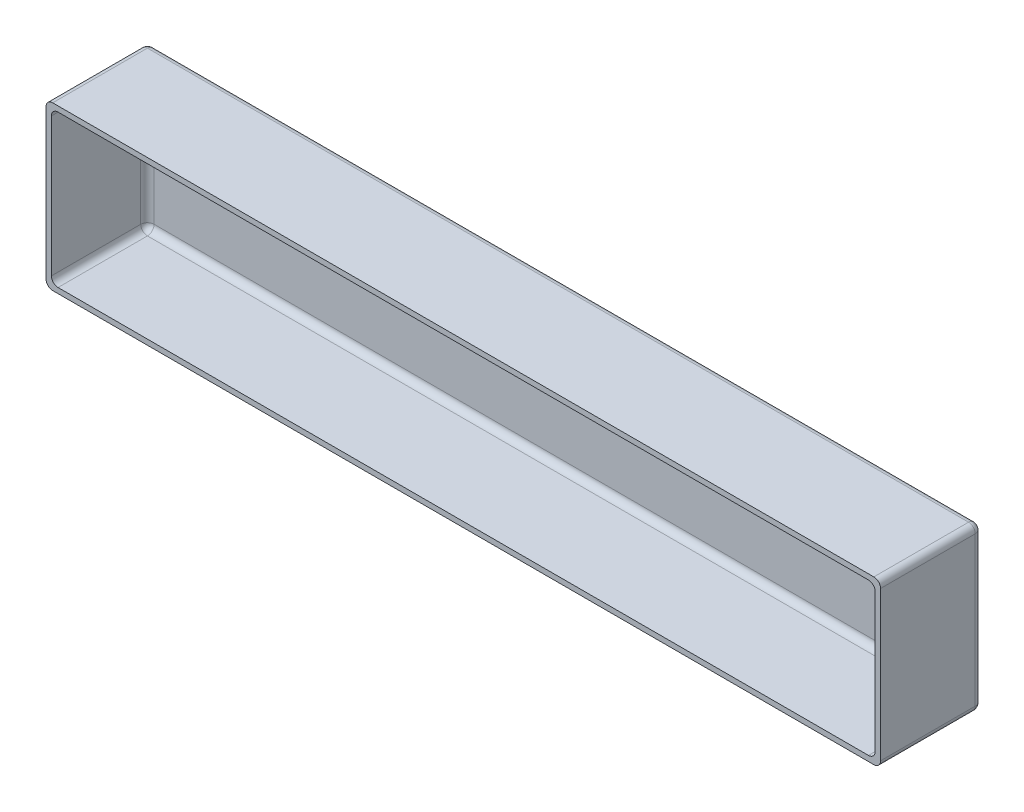
SolidWorks part; units mm, degrees
material "NEOPRENE"
ref_plane "Front" through (0, 0, 0) normal (0, 0, 1) x (1, 0, 0)
ref_plane "Top" through (0, 0, 0) normal (0, 1, 0) x (1, 0, 0)
ref_plane "Right" through (0, 0, 0) normal (1, 0, 0) x (0, 0, -1)
sketch "Sketch1" plane through (0, 0, 0) normal (0, 0, 1) x (1, 0, 0)
  line L1 (-118.618, -23.114) -> (118.618, -23.114)
  line L2 (-118.618, -23.114) -> (-118.618, 23.114)
  line L3 (-118.618, 23.114) -> (118.618, 23.114)
  line L4 (118.618, -23.114) -> (118.618, 23.114)
  line L5 (-118.618, -23.114) -> (118.618, 23.114) construction
  line L6 (-118.618, 23.114) -> (118.618, -23.114) construction
  point P0 (0, 0)
  dimension "D1" = 46.228
  dimension "D2" = 237.236
extrude "Boss-Extrude1" add sketch "Sketch1" along normal blind 28.829
shell "Shell1" thickness 1.524 removed face at (0, 0, 28.829)
fillet "Fillet1" radius 1.905 8 edges at (0, -21.59, 1.524) (-117.094, 0, 1.524) (0, 21.59, 1.524) (117.094, 0, 1.524) (117.094, -21.59, 15.1765) (117.094, 21.59, 15.1765) (-117.094, -21.59, 15.1765) (-117.094, 21.59, 15.1765)
fillet "Fillet2" radius 1.905 8 edges at (118.618, 0, 0) (-118.618, 0, 0) (0, 23.114, 0) (-118.618, 23.114, 14.4145) (-118.618, -23.114, 14.4145) (0, -23.114, 0) (118.618, -23.114, 14.4145) (118.618, 23.114, 14.4145)
